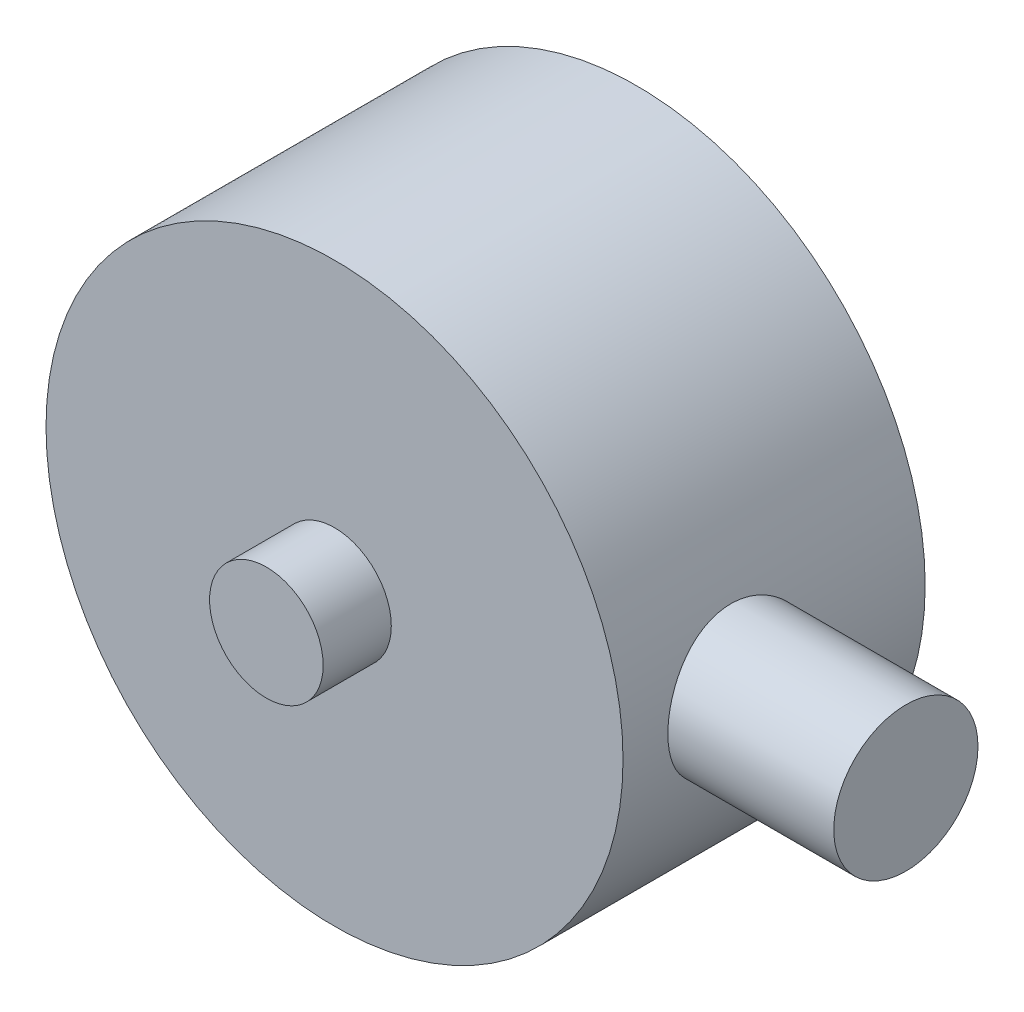
SolidWorks part; units mm, degrees
ref_plane "Front Plane" through (0, 0, 0) normal (0, 0, 1) x (1, 0, 0)
ref_plane "Top Plane" through (0, 0, 0) normal (0, 1, 0) x (1, 0, 0)
ref_plane "Right Plane" through (0, 0, 0) normal (1, 0, 0) x (0, 0, -1)
sketch "Sketch1" plane through (0, 0, 0) normal (0, 0, 1) x (1, 0, 0)
  circle A0 centre (0, 0) radius 12.7
  circle A2 centre (0, 0) radius 2.5
  dimension "D1" = 25.4
  dimension "D2" = 5
extrude "Boss-Extrude1" add sketch "Sketch1" along normal blind 13.3 contours A2 | A0 A2 region at (-12.3408, 0, 0) region at (0, 0, 0)
extrude "Boss-Extrude2" add sketch "Sketch1<3>" along normal blind 16.3 and the other way blind 6.35 contours A2 region at (0, 0, 0)
sketch "Sketch1<3>" plane through (0, 0, 0) normal (0, 0, 1) x (1, 0, 0) same geometry as "Sketch1"
sketch "Sketch2" plane through (0, 0, 0) normal (1, 0, 0) x (0, 0, -1)
  line L0 (0, 0) -> (-16.3, 0) construction
  line L1 (-16.3, 2.5) -> (-16.3, -2.5) construction
  circle A0 centre (-8.15, 0) radius 3.175
  dimension "D1" = 6.35
extrude "Boss-Extrude3" add sketch "Sketch2" along normal blind 20
